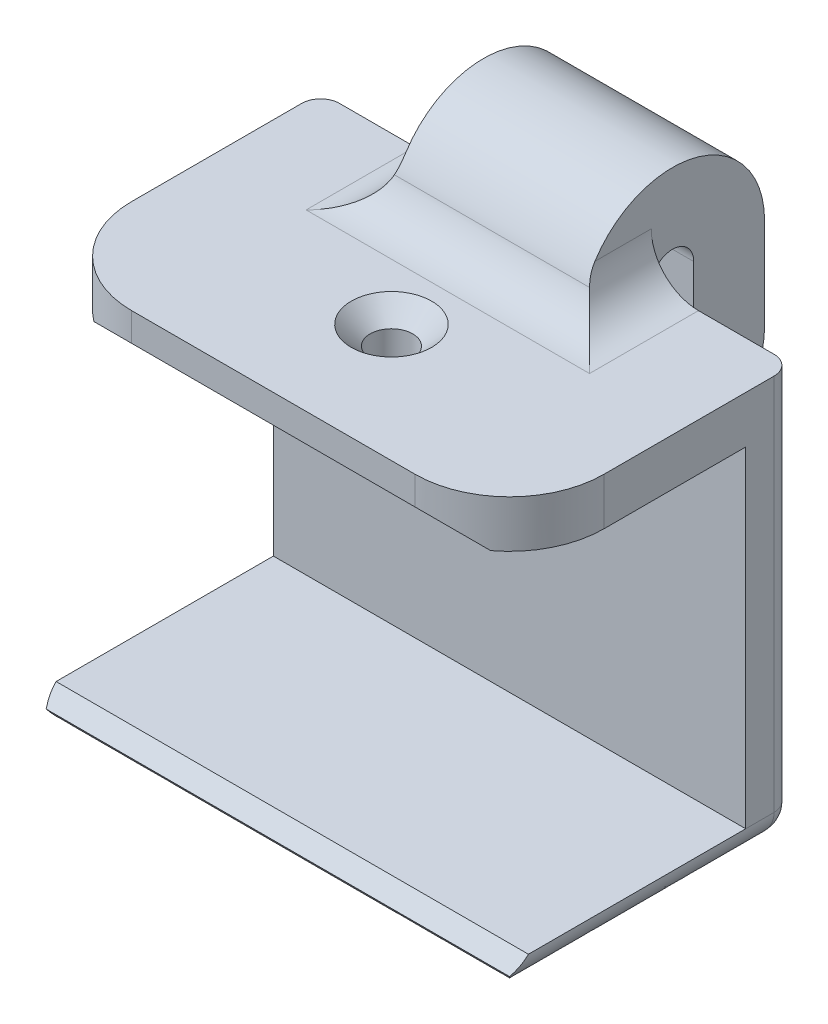
SolidWorks part; units mm, degrees
ref_plane "Front Plane" through (0, 0, 0) normal (0, 0, 1) x (1, 0, 0)
ref_plane "Top Plane" through (0, 0, 0) normal (0, 1, 0) x (1, 0, 0)
ref_plane "Right Plane" through (0, 0, 0) normal (1, 0, 0) x (0, 0, -1)
sketch "Sketch1" plane through (0, 0, 0) normal (-1, 0, 0) x (0, 1, 0)
  line L0 (-35, 0) -> (0, 0)
  line L1 (0, 0) -> (0, -25)
  line L2 (-35, -15) -> (-35, -25)
  line L3 (-9, 5) -> (4.75, 5)
  line L4 (4.75, 9.5) -> (-9, 9.5)
  line L5 (-9, 5) -> (-9, 9.5)
  line L6 (-9, 17) -> (4.75, 17)
  line L7 (5, -2.4968) -> (5, -25)
  line L8 (5, -25) -> (0, -25)
  line L9 (4.75, 9.5) -> (4.75, 5) construction
  line L10 (-9, 17) -> (-21, 5)
  line L11 (-9, 17) -> (-9, 9.5) construction
  line L12 (-21, 5) -> (-9, 5) construction
  line L13 (-35, 0) -> (-35, -15)
  line L15 (-40, -15) -> (-40, 3)
  line L16 (-38, 5) -> (-21, 5)
  arc A0 (4.75, 5) -> (4.75, 9.5) centre (4.75, 7.25) ccw
  arc A1 (5, -2.4968) -> (4.75, 17) centre (4.75, 7.25) ccw
  arc A2 (-40, 3) -> (-38, 5) centre (-38, 3) cw
  ellipse E0 centre (-35, -15) end of major axis (-35, -25) minor radius 5 (-40, -15) -> (-35, -25) ccw
  point P10 (7, 7.25)
  point P17 (0, -12.5)
  dimension "D3" = 4.5
  dimension "D5" = 7.5
  dimension "D8" = 35
  dimension "D14" = 2
  dimension "D2" = 5
  dimension "D4" = 7
  dimension "D6" = 9
  dimension "D7" = 5
  dimension "D9" = 25
  dimension "D10" = 15
  dimension "D11" = 12
  dimension "D12" = 5
  dimension "D13" = 10
extrude "Boss-Extrude1" add sketch "Sketch1" along normal blind 10 and the other way blind 10
sketch "Sketch3" plane through (0, 0, 0) normal (1, 0, 0) x (0, 0, -1)
  line L0 (0, 0) -> (0, -35)
  line L1 (0, 0) -> (-25, 0)
  line L2 (-15, -35) -> (-15, -40) construction
  line L3 (5, 5) -> (-25, 5)
  line L4 (-25, 0) -> (-25, 5)
  line L5 (0, -35) -> (-25, -35)
  line L6 (-25, -35) -> (0, -35) construction
  line L7 (-25, 0) -> (-25, 5) construction
  line L8 (-15, -40) -> (3, -40)
  line L9 (-25, 5) -> (-2.4968, 5) construction
  line L10 (5, -38) -> (5, 5)
  line L11 (5, -9) -> (5, 4.75) construction
  arc A0 (5, -38) -> (3, -40) centre (3, -38) cw
  ellipse E0 centre (-15, -35) end of major axis (-25, -35) minor radius 5 (-25, -35) -> (-15, -40) ccw construction
  ellipse E1 centre (-15, -35) end of major axis (-5, -35) minor radius 5 (-25, -35) -> (-15, -40) ccw
  point P24 (0, 0)
  point P31 (-25, 4.75)
  point P34 (0, 0)
  point P35 (-25, 5)
  point P38 (3.8364, 5)
  dimension "D1" = 2
extrude "Boss-Extrude2" add sketch "Sketch3" along normal blind 25 and the other way blind 25
sketch "Sketch5" plane through (0, 5, 0) normal (0, 1, 0) x (1, 0, 0)
  line L0 (25, -25) -> (-25, -25) construction
  line L4 (0, 0) -> (0, -25) construction
  circle A1 centre (0, -12.5) radius 2.25
  dimension "D1" = 4.5
extrude "Cut-Extrude1" cut sketch "Sketch5" against normal blind 5
chamfer "Chamfer1" distance 2 angle 45 1 edges at (0, 5, 14.75)
fillet "Fillet1" radius 5 3 edges at (-10, 5, -1.2516) (10, 5, -1.2516) (0, 5, 2.4968)
sketch "Sketch7" plane through (0, 0, -5) normal (0, 0, -1) x (-1, 0, 0)
  line L2 (-25, -40) -> (25, -40) construction
  line L3 (-25, -38) -> (-25, 5) construction
  line L4 (-25, -35) -> (-15, -35) construction
  line L5 (-25, -35) -> (-25, -40)
  line L6 (-25, -40) -> (-15, -40)
  line L7 (0, -9) -> (0, -21) construction
  line L8 (-10, -9) -> (10, -9) construction
  line L9 (-10, -21) -> (10, -21) construction
  line L10 (25, -35) -> (15, -35) construction
  line L11 (25, -40) -> (15, -40)
  line L12 (25, -35) -> (25, -40)
  ellipse E0 centre (-15, -35) end of major axis (-5, -35) minor radius 5 (-25, -35) -> (-15, -40) ccw
  ellipse E1 centre (15, -35) end of major axis (5, -35) minor radius 5 (25, -35) -> (15, -40) cw
  dimension "D1" = 10
  dimension "D2" = 5
extrude "Cut-Extrude3" cut sketch "Sketch7" against normal blind 57
fillet "Fillet3" radius 2 4 edges at (25, -15, -5) (-25, -15, -5) (24.4868, -36.5811, -5) (-24.4868, -36.5811, -5)
fillet "Fillet4" radius 10 2 edges at (0, -9, -17) (0, -21, -5)
fillet "Fillet5" radius 10 2 edges at (10, -17.0711, -5) (-10, -17.0711, -5)
fillet "Fillet6" radius 10 2 edges at (25, 2.5, 25) (-25, 2.5, 25)
sketch "Sketch8" plane through (-25, 0, 0) normal (-1, 0, 0) x (0, 0, 1)
  line L0 (25, 2) -> (23, 0)
  line L1 (25, 5) -> (25, 0) construction
  line L2 (15, 0) -> (25, 0) construction
  line L3 (23, 0) -> (25, 0)
  line L4 (25, 0) -> (25, 2)
  line L5 (23, -35) -> (25, -35)
  line L6 (0, -35) -> (25, -35) construction
  line L7 (25, -35) -> (25, -37)
  line L8 (25, -37) -> (23, -35)
  dimension "D1" = 2
  dimension "D2" = 2
extrude "Cut-Extrude4" cut sketch "Sketch8" against normal blind 67
